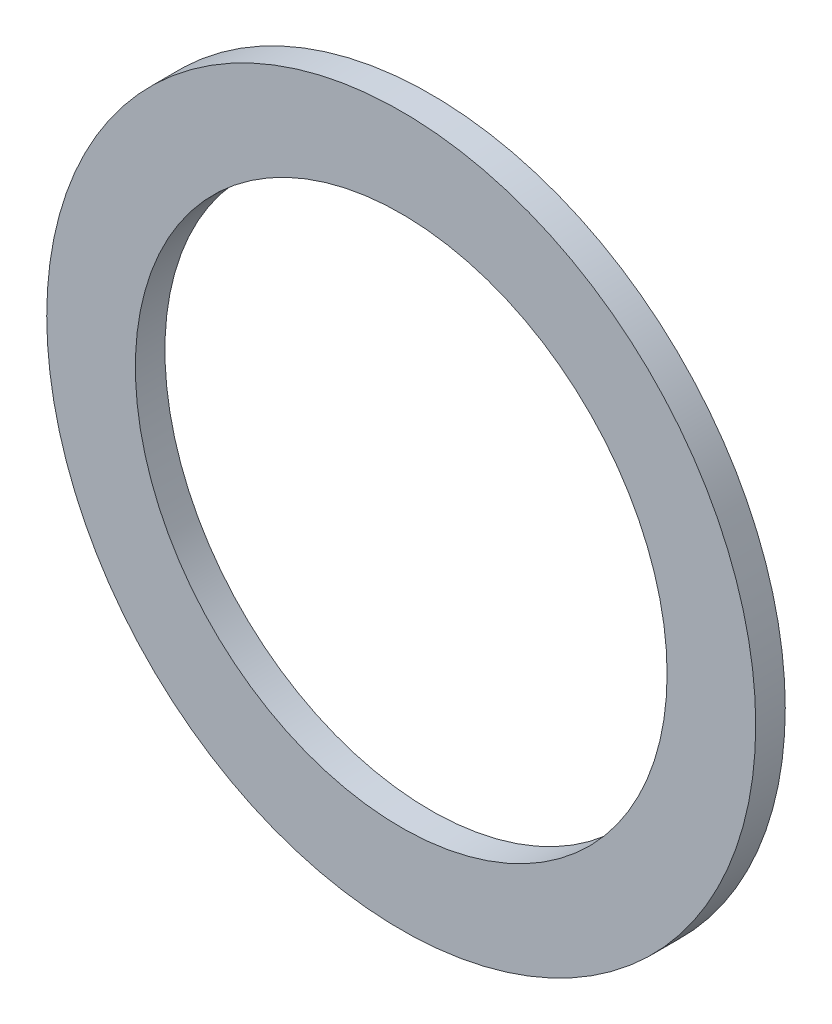
SolidWorks part; units mm, degrees
ref_plane "Front Plane" through (0, 0, 0) normal (0, 0, 1) x (1, 0, 0)
ref_plane "Top Plane" through (0, 0, 0) normal (0, 1, 0) x (1, 0, 0)
ref_plane "Right Plane" through (0, 0, 0) normal (1, 0, 0) x (0, 0, -1)
sketch "Sketch1" plane through (0, 0, 0) normal (0, 0, 1) x (1, 0, 0)
  circle A0 centre (0, 0) radius 38.1
  circle A1 centre (0, 0) radius 28.575
  dimension "D1" = 57.15
  dimension "D2" = 76.2
extrude "Boss-Extrude1" add sketch "Sketch1" along normal blind 3.175
equation "\"AIRFRAME_OD\"= 3.091in"
equation "\"AIRFRAME_ID\"= 3.00in"
equation "\"FLAT_T\" = 0.125in"
equation "\"COUPLER_OD\" = 2.998in"
equation "\"COUPLER_ID\" = 2.875in"
equation "\"NOSE_EXP_L\"= 3.5in"
equation "\"NOSE_SHOULDER_L\" = 5in"
equation "\"MAIN_L\" = 30in"
equation "\"RECO_COUP_L\" = 6in"
equation "\"RECO_SWITCH_L\" = 1.5in"
equation "\"RECO_ROD_X\" = 1.5in"
equation "\"DROGUE_L\" = 14in"
equation "\"ATS_FORE_COUP_L\" = 4in"
equation "\"ATS_AFT_COUP_L\" = 4in"
equation "\"ATS_ROD_X\" = 2in"
equation "\"LOWER_L\" = 16in"
equation "\"FIN_ROOT\" = 5in"
equation "\"FIN_X\" = 0.75in"
equation "\"FIN_N\" = 4"
equation "\"MOTOR_OD\" = 2.25in"
equation "\"MOTOR_ID\" = 2.126in"
equation "\"MOTOR_L\" = 8in"
equation "\"CR_AFT_X\" = 0.5in"
equation "\"CR_FORE_X\" = 6in"
equation "\"D1@Boss-Extrude1\"=\"FLAT_T\""
equation "\"D1@Sketch1\"=\"MOTOR_OD\""
equation "\"D2@Sketch1\"=\"AIRFRAME_ID\""
